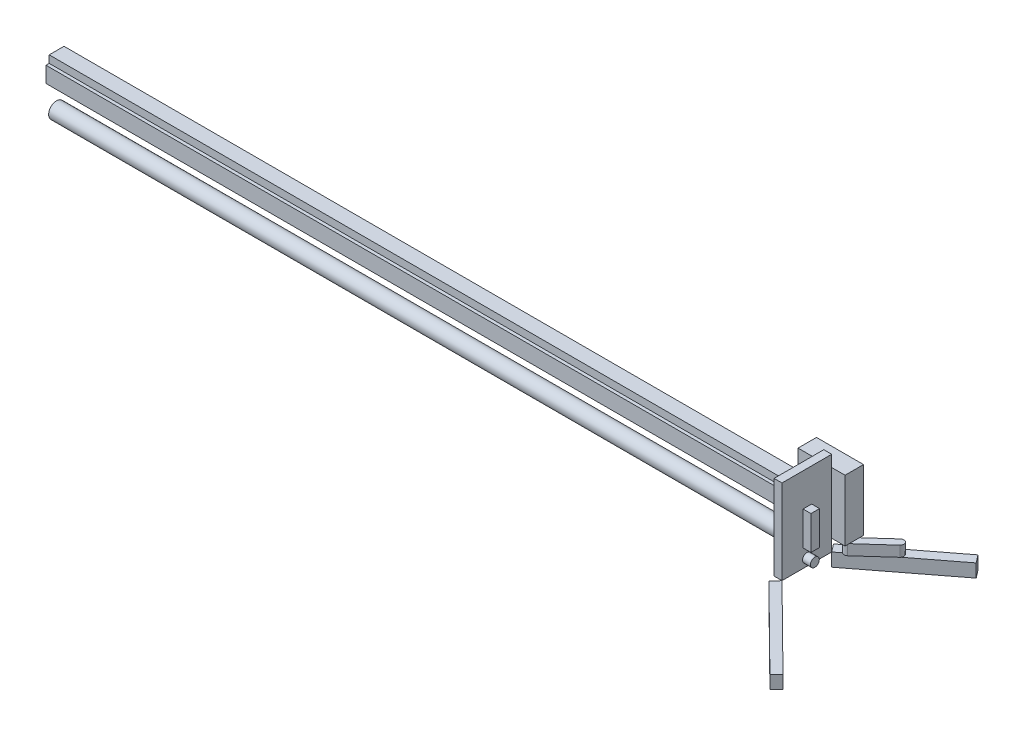
SolidWorks part; units mm, degrees
ref_plane "Front Plane" through (0, 0, 0) normal (0, 0, 1) x (1, 0, 0)
ref_plane "Top Plane" through (0, 0, 0) normal (0, 1, 0) x (1, 0, 0)
ref_plane "Right Plane" through (0, 0, 0) normal (1, 0, 0) x (0, 0, -1)
sketch "Sketch2" plane through (0, 0, 0) normal (-1, 0, 0) x (0, 0, 1)
  line L3 (-19.8706, 17.881) -> (-11.8706, 17.881)
  line L4 (-11.8706, 23.881) -> (-11.8706, 17.881)
  line L9 (-19.8706, 17.881) -> (-19.8706, 23.881)
  line L10 (-19.8706, 23.881) -> (-18.7033, 23.881)
  line L11 (-18.7033, 23.881) -> (-18.7033, 26.685)
  line L13 (-13.0867, 26.685) -> (-13.0867, 23.881)
  line L14 (-13.0867, 23.881) -> (-11.8706, 23.881)
  line L16 (-18.7033, 26.685) -> (-13.0867, 26.685)
  circle A0 centre (-15.8706, 7.1987) radius 3
  dimension "D1" = 6
  dimension "D2" = 8
extrude "Boss-Extrude1" add sketch "Sketch2" against normal blind 282
sketch "Sketch3" plane through (282, 0, 0) normal (1, 0, 0) x (0, 0, -1)
  line L1 (6.0161, 32.098) -> (24.8682, 32.098)
  line L2 (6.0161, 32.098) -> (6.0161, 0)
  line L3 (6.0161, 0) -> (24.8682, 0)
  line L4 (24.8682, 32.098) -> (24.8682, 0)
extrude "Boss-Extrude2" add sketch "Sketch3" along normal blind 3
sketch "Sketch4" plane through (0, 0, 0) normal (0, -1, 0) x (1, 0, 0)
  line L1 (285, -24.8682) -> (315.9936, -48.672)
  line L2 (315.9936, -48.672) -> (313.6963, -51.663)
  line L3 (313.6963, -51.663) -> (282.7028, -27.8592)
  line L6 (285, -6.0161) -> (315.9936, 24.5946)
  line L7 (315.9936, 24.5946) -> (313.5285, 27.0906)
  line L8 (313.5285, 27.0906) -> (282.7028, -3.3543)
  line L10 (282.7028, -3.3543) -> (285, -6.0161)
  line L11 (285, -24.8682) -> (282.7028, -27.8592)
  point P0 (282.7028, -3.3543)
extrude "Boss-Extrude3" add sketch "Sketch4" along normal blind 5 separate body
sketch "Sketch5" plane through (0, 0, -24.8682) normal (0, 0, -1) x (-1, 0, 0)
  line L1 (-290.0706, 27.7483) -> (-272.2342, 27.7483)
  line L2 (-290.0706, 27.7483) -> (-290.0706, 4.4881)
  line L3 (-290.0706, 4.4881) -> (-272.2342, 4.4881)
  line L4 (-272.2342, 27.7483) -> (-272.2342, 4.4881)
extrude "Boss-Extrude4" add sketch "Sketch5" along normal blind 7
sketch "Sketch6" plane through (0, 4.4881, 0) normal (0, -1, 0) x (1, 0, 0)
  line L0 (288.7866, -27.2256) -> (299.1833, -36.6076) construction
  line L1 (289.7555, -26.152) -> (300.1522, -35.534)
  line L2 (287.8177, -28.2993) -> (298.2144, -37.6813)
  arc A0 (289.7555, -26.152) -> (287.8177, -28.2993) centre (288.7866, -27.2256) ccw
  arc A1 (298.2144, -37.6813) -> (300.1522, -35.534) centre (299.1833, -36.6076) ccw
  point P2 (293.9849, -31.9166)
extrude "Boss-Extrude5" add sketch "Sketch6" along normal blind 4
sketch "Sketch7" plane through (285, 0, 0) normal (1, 0, 0) x (0, 0, -1)
  line L6 (14.0043, 19.5486) -> (17.2679, 19.5486)
  line L7 (14.0043, 19.5486) -> (14.0043, 6.7547)
  line L8 (14.0043, 6.7547) -> (17.2679, 6.7547)
  line L9 (17.2679, 19.5486) -> (17.2679, 6.7547)
  circle A0 centre (15.4804, 2.8231) radius 1.6789
  point P2 (15.4804, 2.8231)
extrude "Boss-Extrude6" add sketch "Sketch7" along normal blind 3
